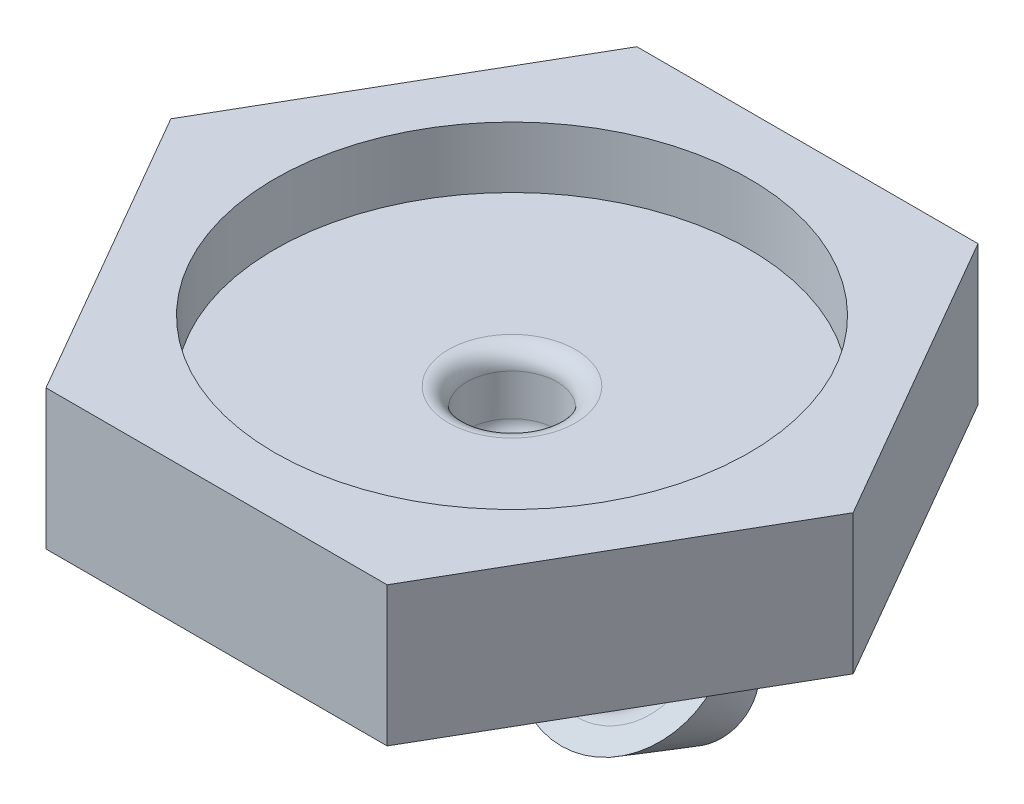
SolidWorks part; units mm, degrees
ref_plane "Front Plane" through (0, 0, 0) normal (0, 0, 1) x (1, 0, 0)
ref_plane "Top Plane" through (0, 0, 0) normal (0, 1, 0) x (1, 0, 0)
ref_plane "Right Plane" through (0, 0, 0) normal (1, 0, 0) x (0, 0, -1)
sketch "Sketch11" plane through (0, 0, 0) normal (0, 1, 0) x (1, 0, 0)
  line L7 (18.3309, 0) -> (9.1654, 15.875)
  line L8 (9.1654, 15.875) -> (-9.1654, 15.875)
  line L9 (-9.1654, 15.875) -> (-18.3309, 0)
  line L10 (-18.3309, 0) -> (-9.1654, -15.875)
  line L11 (-9.1654, -15.875) -> (9.1654, -15.875)
  line L12 (9.1654, -15.875) -> (18.3309, 0)
  circle A0 centre (0, 0) radius 15.875 construction
  dimension "D1" = 31.75
extrude "MainHolder" add sketch "Sketch11" along normal blind 7.5
sketch "Sketch12" plane through (0, 7.5, 0) normal (0, 1, 0) x (1, 0, 0)
  circle A0 centre (0, 0) radius 12.75
  dimension "D1" = 25.5
extrude "MagnetCutout" cut sketch "Sketch12" against normal blind 3.28
sketch "Sketch13" plane through (0, 4.22, 0) normal (0, 1, 0) x (1, 0, 0)
  circle A0 centre (0, 0) radius 2.415
  dimension "D1" = 4.83
extrude "MagnetHole" cut sketch "Sketch13" against normal up to next
sketch "DrainPath" plane through (0, 0, 0) normal (1, 0, 0) x (0, 0, -1)
  line L0 (0, 0) -> (0, -2)
  line L1 (1.7574, -6.2426) -> (10.2426, -14.7279)
  arc A0 (1.7574, -6.2426) -> (0, -2) centre (6, -2) cw
  point P7 (0, -4.4853)
  dimension "D3" = 6
  dimension "D1" = 135
  dimension "D2" = 12
  dimension "D4" = 2
sketch "DrainOpening" plane through (0, 0, 0) normal (0, -1, 0) x (1, 0, 0)
  circle A0 centre (0, 0) radius 1.125
  circle A2 centre (0, 0) radius 2.5
  dimension "D1" = 2.25
  dimension "D2" = 5
sweep "Drain" add profiles "DrainOpening" path "DrainPath"
ref_axis "DrainOutAxis" through (0, -5.4471, -0.9619) along (0, -0.7071, -0.7071)
ref_plane "DrainMidPlain" through (0, 0, 0) normal (-1, 0, 0) x (0, -0.7071, -0.7071)
sketch "BarbOutline" plane through (0, 0, 0) normal (-1, 0, 0) x (0, -0.7071, -0.7071)
  line L0 (17.6569, 0.6716) -> (11.6569, 0.6716)
  line L1 (11.6569, 0.6716) -> (11.6569, -1.5784)
  line L2 (11.6569, -1.5784) -> (17.6569, 0.6716)
  line L3 (5.6569, 0.6716) -> (17.6569, 0.6716) construction
  line L4 (4.5319, 3.1716) -> (18.7819, 3.1716) construction
  point P6 (0, 0)
  dimension "D1" = 6
  dimension "D2" = 4.75
revolve "Barb" add sketch "BarbOutline" angle 360 about axis through (0, -5.4471, -0.9619) along (0, -0.7071, -0.7071)
ref_axis "MagnetAxis" through (0, 0, 0) along (0, 1, 0)
fillet "DrainBaseFillet" radius 2 1 edges at (0, 0, -2.5) type face fillet first side face at (0, 0, -2.5) second side face at (0, -2, -2.5)
fillet "BarbBaseFillet" radius 1 1 edges at (0, -12.253, -4.2322) type face fillet first side face at (0, -13.844, -2.6412) second side face at (0, -12.253, -4.2322)
fillet "DrainOpenFillet" radius 1 1 edges at (0, 0, -2.415) type face fillet first side face at (0, 4.22, 2.415) second side face at (0, 0, -1.125)
fillet "MagnetFillet" radius 1 1 edges at (0, 4.22, 2.415) type face fillet first side face at (0, 4.22, 2.415) second side face at (0, 1, -2.415)
equation "\"channel_diameter\"= 4mm"
equation "\"channel_length\"= 12mm"
equation "\"barb_large_diameter\"= 4.75mm"
equation "\"barb_length\"= 6mm"
equation "\"lumen_diameter\"= 2.25mm"
equation "\"magnet_holder_thickness\"= 7.5"
equation "\"magnet_diameter\"=25.4"
equation "\"magnet_holder_tolerance\"= 0.1mm"
equation "\"magnet_thickness\"= 3.18mm"
equation "\"D1@Sketch11\"=\"magnet_diameter\" * 1.25"
equation "\"D1@MainHolder\" = \"magnet_holder_thickness\""
equation "\"D1@Sketch12\"=\"magnet_diameter\" + \"magnet_holder_tolerance\""
equation "\"D1@MagnetCutout\" = \"magnet_thickness\" + \"magnet_holder_tolerance\""
equation "\"magnet_hole_small\"= 4.83mm"
equation "\"D1@Sketch13\"=\"magnet_hole_small\""
equation "\"drain_angle\"= 135"
equation "\"D1@DrainPath\" = \"drain_angle\""
equation "\"D2@DrainPath\" = \"barb_length\" * 2"
equation "\"D1@DrainOpening\" = \"lumen_diameter\""
equation "\"D1@BarbOutline\" = \"barb_length\""
equation "\"D2@BarbOutline\"=\"barb_large_diameter\""
equation "\"FilletBase\"=3"
